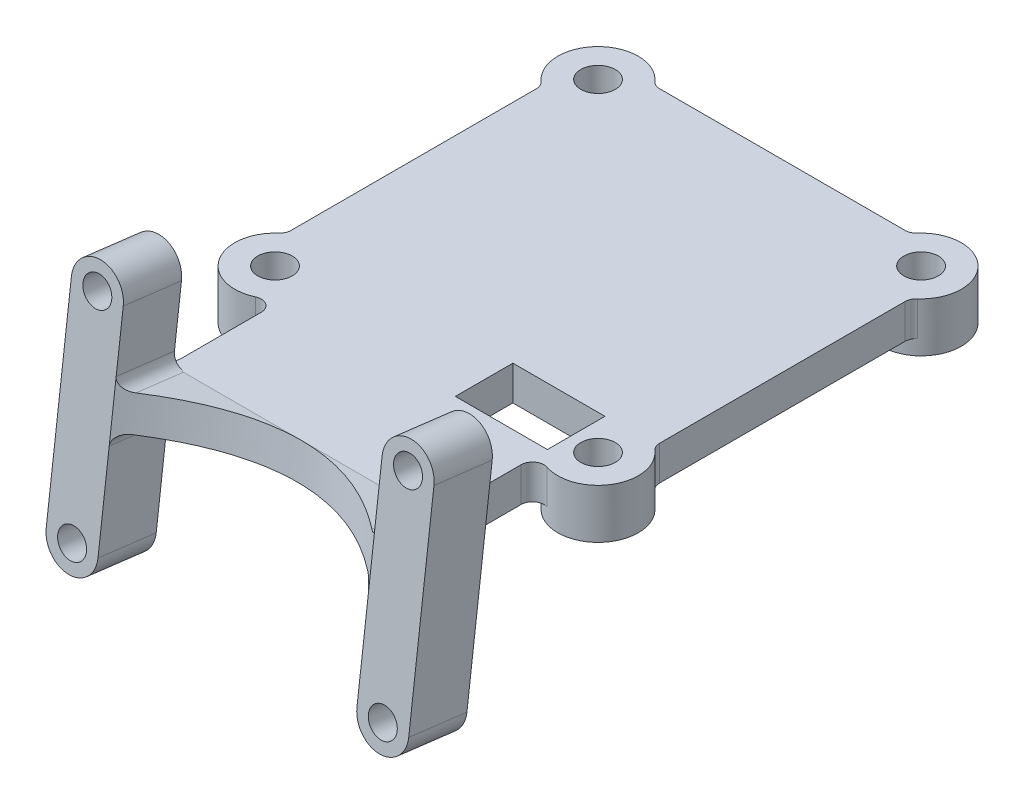
SolidWorks part; units mm, degrees
ref_plane "Front Plane" through (0, 0, 0) normal (0, 0, 1) x (1, 0, 0)
ref_plane "Top Plane" through (0, 0, 0) normal (0, 1, 0) x (1, 0, 0)
ref_plane "Right Plane" through (0, 0, 0) normal (1, 0, 0) x (0, 0, -1)
sketch "Sketch1" plane through (0, 0, 0) normal (0, 1, 0) x (1, 0, 0)
  line L0 (-16.0143, 16.0143) -> (-16.0143, 11.1488) construction
  line L1 (11.1488, 16.0143) -> (-11.1488, 16.0143)
  line L2 (16.0143, 11.1488) -> (16.0143, -11.1488)
  line L4 (-16.0143, 11.1488) -> (-16.0143, -11.1488)
  line L5 (16.0143, 16.0143) -> (-16.0143, -16.0143) construction
  line L6 (15.9857, -15.9857) -> (-16.0143, 16.0143) construction
  line L7 (-16.0143, 16.0143) -> (-11.1488, 16.0143) construction
  line L8 (16.0143, 16.0143) -> (16.0143, 11.0332) construction
  line L9 (16.0143, 16.0143) -> (11.1488, 16.0143) construction
  line L10 (15.9857, -15.9857) -> (11.6143, -15.9857) construction
  line L11 (15.9857, -15.9857) -> (16.0143, -11.1488) construction
  line L12 (-16.0143, -16.0143) -> (-16.0143, -11.1488) construction
  line L15 (11.6143, -11.0143) -> (3.6143, -11.0143)
  line L16 (11.6143, -11.0143) -> (11.6143, -15.9857)
  line L18 (3.6143, -11.0143) -> (3.6143, -16.0143)
  line L19 (11.6143, -11.0143) -> (3.6143, -16.0143) construction
  line L20 (11.6143, -15.9857) -> (3.6143, -11.0143) construction
  line L21 (11.6143, -15.9857) -> (11.6143, -16.0143)
  line L22 (-11.1488, -26.0143) -> (11.6143, -26.0143)
  line L23 (-11.1488, -26.0143) -> (-11.1488, -16.0143)
  line L24 (3.6143, -16.0143) -> (11.6143, -16.0143)
  line L25 (11.6143, -26.0143) -> (11.6143, -16.5629)
  line L26 (-11.1488, -26.0143) -> (11.6143, -16.0143) construction
  line L27 (-11.1488, -16.0143) -> (11.6143, -26.0143) construction
  circle A0 centre (14.0361, 14.0361) radius 1.5
  circle A1 centre (14.0361, -14.0361) radius 1.5
  circle A2 centre (-14.0361, -14.0361) radius 1.5
  circle A3 centre (-14.0361, 14.0361) radius 1.5
  arc A4 (-11.1488, 16.0143) -> (-16.0143, 11.1488) centre (-14.0361, 14.0361) ccw
  arc A5 (16.0143, 11.1488) -> (11.1488, 16.0143) centre (14.0361, 14.0361) ccw
  arc A6 (11.6143, -16.5629) -> (16.0143, -11.1488) centre (14.0361, -14.0361) ccw
  arc A7 (-16.0143, -11.1488) -> (-11.1488, -16.0143) centre (-14.0361, -14.0361) ccw
  point P0 (0, 0)
  point P3 (0.2328, -21.0143)
  point P8 (-12.9754, -12.9754)
  point P9 (12.9754, 12.9754)
  point P20 (7.6258, -13.5071)
  point P31 (0, 0)
  point P51 (0, 0)
  dimension "D3" = 3
  dimension "D5" = 2
  dimension "D7" = 10
  dimension "D1" = 32
  dimension "D4" = 36.7
  dimension "D8" = 12.4
  dimension "D9" = 8
  dimension "D10" = 5
  dimension "D2" = 45.2953
  dimension "D6" = 4
extrude "Boss-Extrude1" add sketch "Sketch1" along normal blind 2.9967
ref_plane "Plane1" through (0.2328, 0, 0) normal (1, 0, 0) x (0, 0, -1)
sketch "Sketch4" plane through (0, 0, 0) normal (0, -1, 0) x (1, 0, 0)
  line L3 (11.6143, 11.5092) -> (11.6143, 16.5629)
  circle A0 centre (-14.0361, -14.0361) radius 1.5 construction
  circle A1 centre (14.0361, -14.0361) radius 1.5 construction
  circle A2 centre (14.0361, 14.0361) radius 1.5 construction
  circle A3 centre (-14.0361, 14.0361) radius 1.5 construction
  circle A4 centre (-14.0361, -14.0361) radius 1.5
  circle A5 centre (14.0361, -14.0361) radius 1.5
  circle A6 centre (14.0361, 14.0361) radius 1.5
  circle A7 centre (-14.0361, 14.0361) radius 1.5
  circle A8 centre (-14.0361, 14.0361) radius 3.5
  arc A9 (11.6143, 11.5092) -> (11.6143, 16.5629) centre (14.0361, 14.0361) ccw
  circle A10 centre (14.0361, -14.0361) radius 3.5
  circle A11 centre (-14.0361, -14.0361) radius 3.5
extrude "Boss-Extrude3" add sketch "Sketch4" along normal blind 1.3
ref_plane "Plane3" through (0, 3.1912, 25.9904) normal (0, 0.1219, 0.9925) x (1, 0, 0)
sketch "Sketch7" plane through (0, 3.1912, 25.9904) normal (0, 0.1219, 0.9925) x (1, 0, 0)
  line L0 (0.2328, 4.1778) -> (0.2328, -10.5185) construction
  line L1 (0.2328, -3.1703) -> (-15.5172, -3.1703) construction
  line L2 (-11.0172, 5.8297) -> (-11.0172, -0.196)
  line L3 (-15.5172, 5.8297) -> (-15.5172, -12.1703)
  line L4 (11.4828, 5.8297) -> (11.4828, -0.196)
  line L5 (15.9828, 5.8297) -> (15.9828, -12.1703)
  line L6 (-11.1488, -3.1703) -> (11.6143, -3.1703) construction
  line L7 (-11.0172, -3.1703) -> (11.4828, -3.1703)
  line L8 (-11.0172, -0.196) -> (11.4828, -0.196)
  line L9 (11.4828, -3.1703) -> (11.4828, -12.1703)
  line L10 (-11.0172, -3.1703) -> (-11.0172, -12.1703)
  line L11 (-11.1488, -0.196) -> (11.6143, -0.196) construction
  line L12 (0.2328, -1.6482) -> (0.2328, 1.6482) construction
  circle A0 centre (-13.2672, 5.8297) radius 1.25
  arc A1 (-11.0172, 5.8297) -> (-15.5172, 5.8297) centre (-13.2672, 5.8297) ccw
  circle A2 centre (-13.2672, -12.1703) radius 1.25
  arc A3 (-11.0172, -12.1703) -> (-15.5172, -12.1703) centre (-13.2672, -12.1703) cw
  circle A4 centre (13.7328, -12.1703) radius 1.25
  arc A5 (11.4828, 5.8297) -> (15.9828, 5.8297) centre (13.7328, 5.8297) cw
  arc A6 (11.4828, -12.1703) -> (15.9828, -12.1703) centre (13.7328, -12.1703) ccw
  circle A7 centre (13.7328, 5.8297) radius 1.25
  point P10 (-15.5172, -3.1703)
  point P15 (-12.25, -3.1703)
  dimension "D1" = 2.5
  dimension "D2" = 1
  dimension "D3" = 27
  dimension "D4" = 18
extrude "Boss-Extrude5" add sketch "Sketch7" along normal blind 5 and the other way blind 0.1
sketch "Sketch9" plane through (0, -3.1467, 0.3864) normal (0, -0.9925, 0.1219) x (1, 0, 0)
  line L0 (-9.7672, 31.1856) -> (-9.7672, 26.1856) construction
  line L1 (-11.0172, 31.1856) -> (11.4828, 31.1856) construction
  line L2 (-9.7672, 26.1856) -> (10.2328, 26.1856) construction
  line L3 (0.2328, 26.1856) -> (0.2328, 31.1856) construction
  line L4 (10.2328, 31.1856) -> (10.2328, 26.1856) construction
  line L5 (-9.7672, 31.1856) -> (10.2328, 31.1856) construction
  line L6 (-11.0172, 31.1856) -> (11.4828, 31.1856)
  spline S0 degree 2 poles (-11.0172, 31.1856) (0.2328, 21.1856) (11.4828, 31.1856) knots 0 0 0 1 1 1
  dimension "D1" = 5
  dimension "D2" = 20
extrude "Cut-Extrude4" cut sketch "Sketch9" against normal through all both and the other way through all
fillet "Fillet3" radius 0.8 2 edges at (-11.1488, 2.5864, 25.9639) (11.6143, 2.5864, 25.9639)
fillet "Fillet4" radius 1 12 edges at (-16.0143, 1.4983, 11.1488) (-16.0143, 1.4983, -11.1488) (11.1488, 1.4983, -16.0143) (16.0143, 1.4983, -11.1488) (-11.1488, 1.4983, -16.0143) (16.0143, 1.4983, 11.1488) (11.6143, 1.4983, 16.5629) (-11.1488, 1.4983, 16.0143) (11.4828, 3.3013, 28.4957) (-11.0172, 3.3013, 28.4957) (11.4828, 0.3431, 28.8085) (-11.0172, 0.3431, 28.8085)
